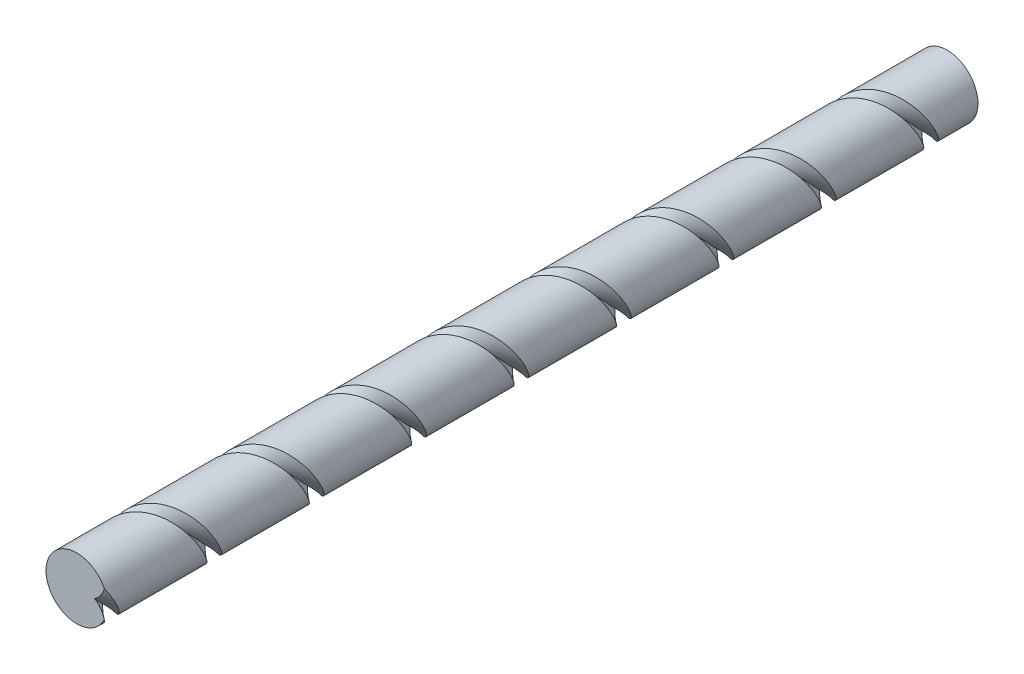
SolidWorks part; units mm, degrees
ref_plane "Alzado" through (0, 0, 0) normal (0, 0, 1) x (1, 0, 0)
ref_plane "Planta" through (0, 0, 0) normal (0, 1, 0) x (1, 0, 0)
ref_plane "Vista lateral" through (0, 0, 0) normal (1, 0, 0) x (0, 0, -1)
sketch "Croquis1" plane through (0, 0, 0) normal (0, 0, 1) x (1, 0, 0)
  circle A0 centre (0, 0) radius 6
  dimension "D1" = 12
extrude "Saliente-Extruir1" add sketch "Croquis1" along normal blind 170
sketch "Croquis2" plane through (0, 0, 170) normal (0, 0, 1) x (1, 0, 0)
  circle A1 centre (0, 0) radius 6
  circle A2 centre (0, 0) radius 6
  dimension "D1" = 0
curve "Hélice/Espiral1" pitch 20 height 1200 turns 60
sketch "Croquis4" plane through (0, 0, 0) normal (0, 1, 0) x (1, 0, 0)
  line L4 (6, -170) -> (6, -168.5566)
  line L5 (6, -170) -> (6, 0) construction
  line L6 (6, -168.5566) -> (3.5, -170)
  line L7 (-6, -170) -> (6, -170) construction
  line L8 (3.5, -170) -> (6, -171.4434)
  line L9 (6, -171.4434) -> (6, -170)
  dimension "D1" = 60
  dimension "D2" = 60
  dimension "D3" = 2.5
sweep "Cortar-Barrer2" cut profiles "Croquis4" path "Hélice/Espiral1"
